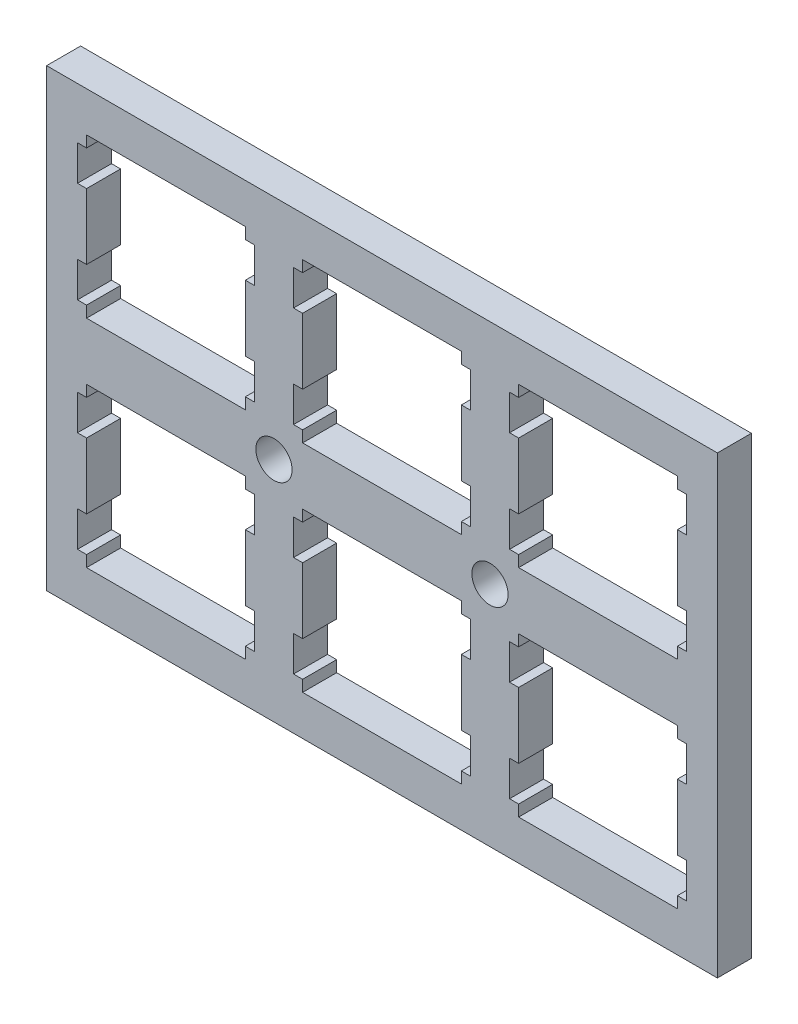
SolidWorks part; units mm, degrees
material "1023 碳钢板 (SS)"
ref_plane "前视基准面" through (0, 0, 0) normal (0, 0, 1) x (1, 0, 0)
ref_plane "上视基准面" through (0, 0, 0) normal (0, 1, 0) x (1, 0, 0)
ref_plane "右视基准面" through (0, 0, 0) normal (1, 0, 0) x (0, 0, -1)
sketch "Model" plane through (0, 0, 0) normal (0, 0, 1) x (1, 0, 0)
  line L0 (-0.9049, 39.3575) -> (58.2453, 39.3575)
  line L1 (58.2453, 39.3575) -> (58.2453, -0.7423)
  line L2 (58.2453, -0.7423) -> (-0.9049, -0.7423)
  line L3 (-0.9049, -0.7423) -> (-0.9049, 39.3575)
  line L4 (40.7197, 16.7831) -> (40.7197, 15.7827)
  line L5 (40.7197, 15.7827) -> (39.9189, 15.7827)
  line L6 (39.9189, 15.7827) -> (39.9189, 12.6835)
  line L7 (39.9189, 12.6835) -> (40.7197, 12.6835)
  line L8 (40.7197, 12.6835) -> (40.7197, 6.8833)
  line L9 (40.7197, 6.8833) -> (39.9189, 6.8833)
  line L10 (39.9189, 6.8833) -> (39.9189, 3.7827)
  line L11 (39.9189, 3.7827) -> (40.7197, 3.7827)
  line L12 (40.7197, 3.7827) -> (40.7197, 2.7836)
  line L13 (40.7197, 2.7836) -> (54.719, 2.7836)
  line L14 (54.719, 2.7836) -> (54.719, 3.7827)
  line L15 (54.719, 3.7827) -> (55.5198, 3.7827)
  line L16 (55.5198, 3.7827) -> (55.5198, 6.8833)
  line L17 (55.5198, 6.8833) -> (54.719, 6.8833)
  line L18 (54.719, 6.8833) -> (54.719, 12.6835)
  line L19 (54.719, 12.6835) -> (55.5198, 12.6835)
  line L20 (55.5198, 12.6835) -> (55.5198, 15.7827)
  line L21 (55.5198, 15.7827) -> (54.719, 15.7827)
  line L22 (54.719, 15.7827) -> (54.719, 16.7831)
  line L23 (54.719, 16.7831) -> (40.7197, 16.7831)
  line L24 (21.6697, 16.7831) -> (21.6697, 15.7827)
  line L25 (21.6697, 15.7827) -> (20.869, 15.7827)
  line L26 (20.869, 15.7827) -> (20.869, 12.6835)
  line L27 (20.869, 12.6835) -> (21.6697, 12.6835)
  line L28 (21.6697, 12.6835) -> (21.6697, 6.8833)
  line L29 (21.6697, 6.8833) -> (20.869, 6.8833)
  line L30 (20.869, 6.8833) -> (20.869, 3.7827)
  line L31 (20.869, 3.7827) -> (21.6697, 3.7827)
  line L32 (21.6697, 3.7827) -> (21.6697, 2.7836)
  line L33 (21.6697, 2.7836) -> (35.669, 2.7836)
  line L34 (35.669, 2.7836) -> (35.669, 3.7827)
  line L35 (35.669, 3.7827) -> (36.4698, 3.7827)
  line L36 (36.4698, 3.7827) -> (36.4698, 6.8833)
  line L37 (36.4698, 6.8833) -> (35.669, 6.8833)
  line L38 (35.669, 6.8833) -> (35.669, 12.6835)
  line L39 (35.669, 12.6835) -> (36.4698, 12.6835)
  line L40 (36.4698, 12.6835) -> (36.4698, 15.7827)
  line L41 (36.4698, 15.7827) -> (35.669, 15.7827)
  line L42 (35.669, 15.7827) -> (35.669, 16.7831)
  line L43 (35.669, 16.7831) -> (21.6697, 16.7831)
  line L44 (2.6197, 16.7831) -> (2.6197, 15.7827)
  line L45 (2.6197, 15.7827) -> (1.819, 15.7827)
  line L46 (1.819, 15.7827) -> (1.819, 12.6835)
  line L47 (1.819, 12.6835) -> (2.6197, 12.6835)
  line L48 (2.6197, 12.6835) -> (2.6197, 6.8833)
  line L49 (2.6197, 6.8833) -> (1.819, 6.8833)
  line L50 (1.819, 6.8833) -> (1.819, 3.7827)
  line L51 (1.819, 3.7827) -> (2.6197, 3.7827)
  line L52 (2.6197, 3.7827) -> (2.6197, 2.7836)
  line L53 (2.6197, 2.7836) -> (16.6192, 2.7836)
  line L54 (16.6192, 2.7836) -> (16.6192, 3.7827)
  line L55 (16.6192, 3.7827) -> (17.4198, 3.7827)
  line L56 (17.4198, 3.7827) -> (17.4198, 6.8833)
  line L57 (17.4198, 6.8833) -> (16.6192, 6.8833)
  line L58 (16.6192, 6.8833) -> (16.6192, 12.6835)
  line L59 (16.6192, 12.6835) -> (17.4198, 12.6835)
  line L60 (17.4198, 12.6835) -> (17.4198, 15.7827)
  line L61 (17.4198, 15.7827) -> (16.6192, 15.7827)
  line L62 (16.6192, 15.7827) -> (16.6192, 16.7831)
  line L63 (16.6192, 16.7831) -> (2.6197, 16.7831)
  line L64 (40.7197, 35.833) -> (40.7197, 34.8327)
  line L65 (40.7197, 34.8327) -> (39.9189, 34.8327)
  line L66 (39.9189, 34.8327) -> (39.9189, 31.7335)
  line L67 (39.9189, 31.7335) -> (40.7197, 31.7335)
  line L68 (40.7197, 31.7335) -> (40.7197, 25.9333)
  line L69 (40.7197, 25.9333) -> (39.9189, 25.9333)
  line L70 (39.9189, 25.9333) -> (39.9189, 22.8327)
  line L71 (39.9189, 22.8327) -> (40.7197, 22.8327)
  line L72 (40.7197, 22.8327) -> (40.7197, 21.8336)
  line L73 (40.7197, 21.8336) -> (54.719, 21.8336)
  line L74 (54.719, 21.8336) -> (54.719, 22.8327)
  line L75 (54.719, 22.8327) -> (55.5198, 22.8327)
  line L76 (55.5198, 22.8327) -> (55.5198, 25.9333)
  line L77 (55.5198, 25.9333) -> (54.719, 25.9333)
  line L78 (54.719, 25.9333) -> (54.719, 31.7335)
  line L79 (54.719, 31.7335) -> (55.5198, 31.7335)
  line L80 (55.5198, 31.7335) -> (55.5198, 34.8327)
  line L81 (55.5198, 34.8327) -> (54.719, 34.8327)
  line L82 (54.719, 34.8327) -> (54.719, 35.833)
  line L83 (54.719, 35.833) -> (40.7197, 35.833)
  line L84 (21.6697, 35.833) -> (21.6697, 34.8327)
  line L85 (21.6697, 34.8327) -> (20.869, 34.8327)
  line L86 (20.869, 34.8327) -> (20.869, 31.7335)
  line L87 (20.869, 31.7335) -> (21.6697, 31.7335)
  line L88 (21.6697, 31.7335) -> (21.6697, 25.9333)
  line L89 (21.6697, 25.9333) -> (20.869, 25.9333)
  line L90 (20.869, 25.9333) -> (20.869, 22.8327)
  line L91 (20.869, 22.8327) -> (21.6697, 22.8327)
  line L92 (21.6697, 22.8327) -> (21.6697, 21.8336)
  line L93 (21.6697, 21.8336) -> (35.669, 21.8336)
  line L94 (35.669, 21.8336) -> (35.669, 22.8327)
  line L95 (35.669, 22.8327) -> (36.4698, 22.8327)
  line L96 (36.4698, 22.8327) -> (36.4698, 25.9333)
  line L97 (36.4698, 25.9333) -> (35.669, 25.9333)
  line L98 (35.669, 25.9333) -> (35.669, 31.7335)
  line L99 (35.669, 31.7335) -> (36.4698, 31.7335)
  line L100 (36.4698, 31.7335) -> (36.4698, 34.8327)
  line L101 (36.4698, 34.8327) -> (35.669, 34.8327)
  line L102 (35.669, 34.8327) -> (35.669, 35.833)
  line L103 (35.669, 35.833) -> (21.6697, 35.833)
  line L104 (2.6197, 35.833) -> (2.6197, 34.8327)
  line L105 (2.6197, 34.8327) -> (1.819, 34.8327)
  line L106 (1.819, 34.8327) -> (1.819, 31.7335)
  line L107 (1.819, 31.7335) -> (2.6197, 31.7335)
  line L108 (2.6197, 31.7335) -> (2.6197, 25.9333)
  line L109 (2.6197, 25.9333) -> (1.819, 25.9333)
  line L110 (1.819, 25.9333) -> (1.819, 22.8327)
  line L111 (1.819, 22.8327) -> (2.6197, 22.8327)
  line L112 (2.6197, 22.8327) -> (2.6197, 21.8336)
  line L113 (2.6197, 21.8336) -> (16.6192, 21.8336)
  line L114 (16.6192, 21.8336) -> (16.6192, 22.8327)
  line L115 (16.6192, 22.8327) -> (17.4198, 22.8327)
  line L116 (17.4198, 22.8327) -> (17.4198, 25.9333)
  line L117 (17.4198, 25.9333) -> (16.6192, 25.9333)
  line L118 (16.6192, 25.9333) -> (16.6192, 31.7335)
  line L119 (16.6192, 31.7335) -> (17.4198, 31.7335)
  line L120 (17.4198, 31.7335) -> (17.4198, 34.8327)
  line L121 (17.4198, 34.8327) -> (16.6192, 34.8327)
  line L122 (16.6192, 34.8327) -> (16.6192, 35.833)
  line L123 (16.6192, 35.833) -> (2.6197, 35.833)
  circle A0 centre (19.1444, 19.3077) radius 1.6
  circle A1 centre (38.1944, 19.3077) radius 1.6
extrude "凸台-拉伸1" add sketch "Model" along normal blind 3
